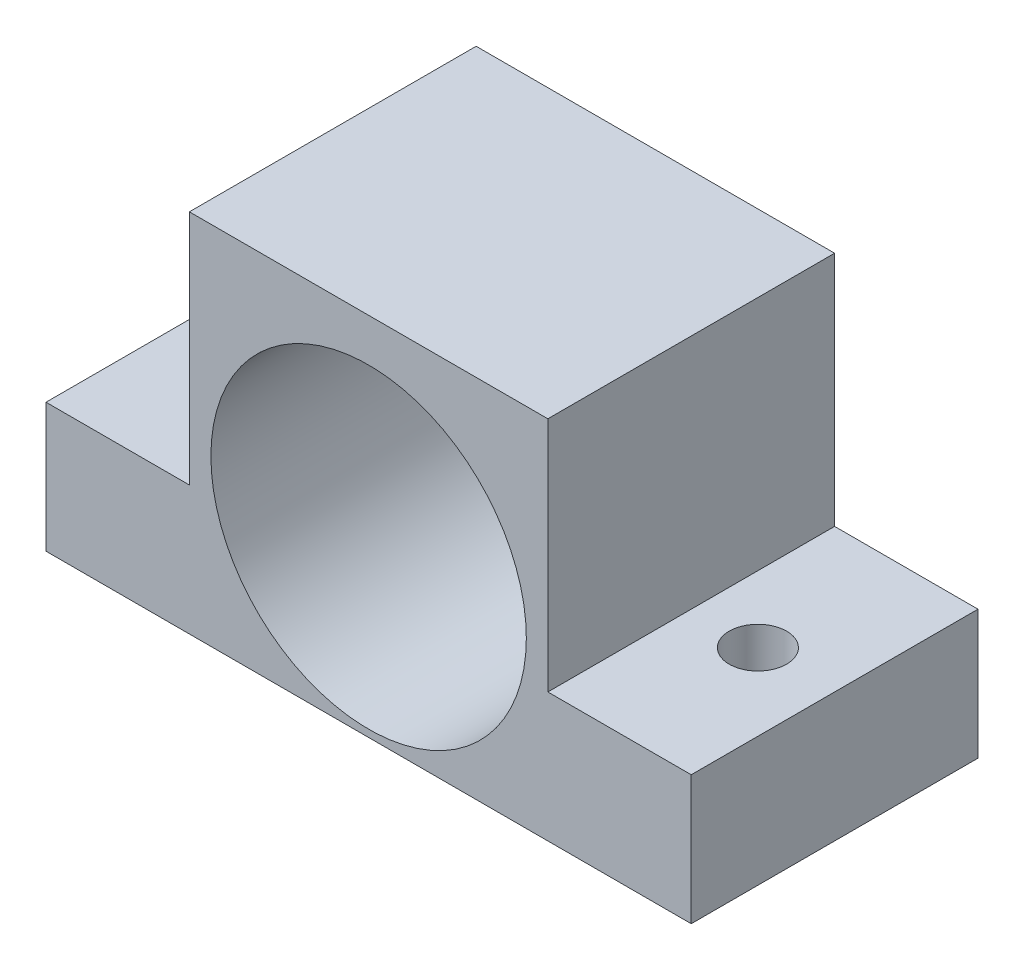
SolidWorks part; units mm, degrees
material "ABS"
ref_plane "Front Plane" through (0, 0, 0) normal (0, 0, 1) x (1, 0, 0)
ref_plane "Top Plane" through (0, 0, 0) normal (0, 1, 0) x (1, 0, 0)
ref_plane "Right Plane" through (0, 0, 0) normal (1, 0, 0) x (0, 0, -1)
sketch "Sketch1" plane through (0, 0, 0) normal (0, 0, 1) x (1, 0, 0)
  line L0 (185.6419, -17.5) -> (-64.3581, -17.5) construction
  line L1 (-11.4483, 8) -> (13.5517, 8)
  line L2 (-11.4483, 8) -> (-11.4483, -17.5)
  line L3 (-11.4483, -17.5) -> (13.5517, -17.5)
  line L4 (13.5517, 8) -> (13.5517, -17.5)
  line L5 (-11.4483, 8) -> (13.5517, -17.5) construction
  line L6 (-11.4483, -17.5) -> (13.5517, 8) construction
  line L7 (13.5517, -17.5) -> (23.5517, -17.5)
  line L8 (13.5517, -17.5) -> (13.5517, -8.5)
  line L9 (13.5517, -8.5) -> (23.5517, -8.5)
  line L10 (23.5517, -17.5) -> (23.5517, -8.5)
  line L11 (13.5517, -17.5) -> (23.5517, -8.5) construction
  line L12 (13.5517, -8.5) -> (23.5517, -17.5) construction
  line L13 (-11.4483, -17.5) -> (-21.4483, -17.5)
  line L14 (-11.4483, -17.5) -> (-11.4483, -8.5)
  line L15 (-11.4483, -8.5) -> (-21.4483, -8.5)
  line L16 (-21.4483, -17.5) -> (-21.4483, -8.5)
  line L17 (-11.4483, -17.5) -> (-21.4483, -8.5) construction
  line L18 (-11.4483, -8.5) -> (-21.4483, -17.5) construction
  circle A0 centre (1.0517, -6) radius 4.1
  circle A1 centre (1.0517, -6) radius 11
  circle A2 centre (1.0517, -6) radius 4 construction
  point P8 (1.0517, -6)
  point P14 (18.5517, -13)
  point P16 (-16.4483, -13)
  dimension "D4" = 8.2
  dimension "D5" = 22
  dimension "D1" = 14
  dimension "D3" = 25
  dimension "D6" = 10
  dimension "D7" = 9
  dimension "D8" = 10
  dimension "D9" = 9
  dimension "D10" = 12.5
extrude "Boss-Extrude1" add sketch "Sketch1" along normal blind 20 contours L4 L1 L2 L3 A1 | L16 L13 L2 L15 | L7 L10 L9 L4 region at (1.0517, 7.6429, 0) region at (-16.4483, -13, 0) region at (18.5517, -13, 0)
sketch "Sketch2" plane through (0, -8.5, 0) normal (0, 1, 0) x (1, 0, 0)
  line L1 (-11.4483, -20) -> (-21.4483, -20)
  line L4 (23.5517, -20) -> (23.5517, 0)
  circle A0 centre (-16.7988, -10) radius 2
  circle A1 centre (18.2012, -10) radius 2
  circle A2 centre (18.2012, -10) radius 2 construction
  circle A3 centre (-16.7988, -10) radius 2 construction
  dimension "D1" = 4
  dimension "D2" = 4
extrude "Cut-Extrude1" cut sketch "Sketch2" against normal blind 9 contours A0 | A0 | A0 | A0 | A1 region at (-16.7988, -8.5, 10)
